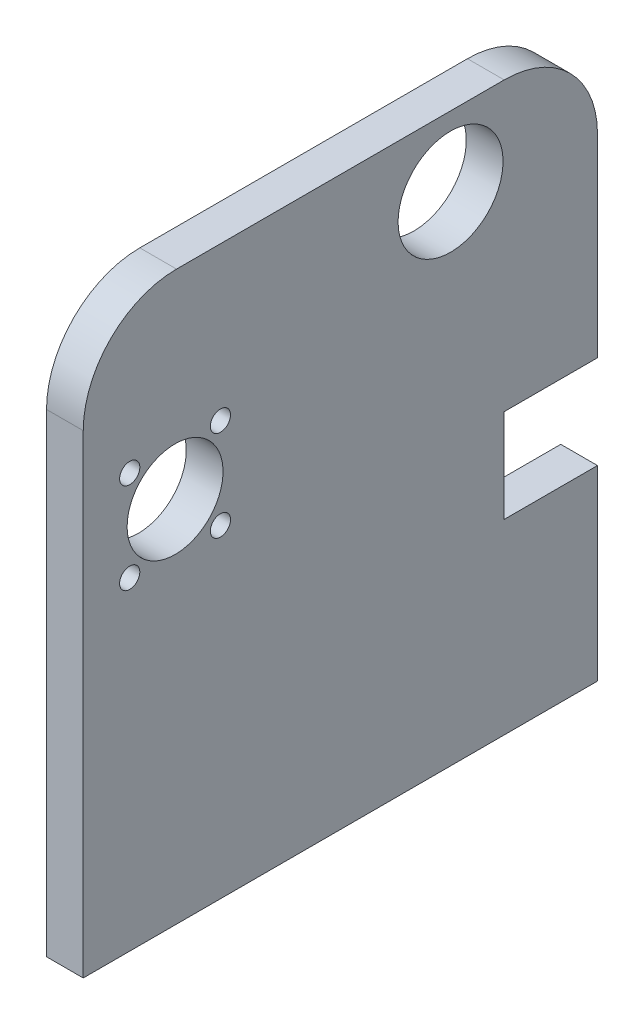
SolidWorks part; units mm, degrees
ref_plane "Front Plane" through (0, 0, 0) normal (0, 0, 1) x (1, 0, 0)
ref_plane "Top Plane" through (0, 0, 0) normal (0, 1, 0) x (1, 0, 0)
ref_plane "Right Plane" through (0, 0, 0) normal (1, 0, 0) x (0, 0, -1)
sketch "Sketch1" plane through (0, 0, 0) normal (0, 1, 0) x (1, 0, 0)
  line L1 (-5, 70) -> (5, 70)
  line L2 (-5, 70) -> (-5, -70)
  line L3 (-5, -70) -> (5, -70)
  line L4 (5, 70) -> (5, -70)
  line L5 (-5, 70) -> (5, -70) construction
  line L6 (-5, -70) -> (5, 70) construction
  point P0 (0, 0)
  dimension "D1" = 140
  dimension "D2" = 10
extrude "Boss-Extrude1" add sketch "Sketch1" along normal mid plane 154.4436
fillet "Fillet1" radius 25.4 2 edges at (0, 77.2218, 70) (0, 77.2218, -70)
sketch "Sketch5" plane through (-5, 0, 0) normal (-1, 0, 0) x (0, 0, 1)
  line L1 (-70, 51.8218) -> (-70, -77.2218) construction
  line L2 (-70, -0.9964) -> (-44.6, -0.9964)
  line L3 (-70, -0.9964) -> (-70, -26.3964)
  line L4 (-70, -26.3964) -> (-44.6, -26.3964)
  line L5 (-70, -77.2218) -> (70, -77.2218) construction
  line L6 (-44.6, -0.9964) -> (-44.6, -26.3964)
  dimension "D3" = 25.4
  dimension "D1" = 50.8254
  dimension "D2" = 25.4
sketch "Sketch3" plane through (-5, 0, 0) normal (-1, 0, 0) x (0, 0, 1)
  line L0 (45, 23.1718) -> (61.409, 39.5809) construction
  line L2 (-70, 51.8218) -> (-70, -77.2218) construction
  line L3 (-45.4613, 23.1718) -> (44.137, 23.1718) construction
  line L6 (45, 46.9613) -> (45, -2.4047) construction
  line L7 (-44.6, 77.2218) -> (44.6, 77.2218) construction
  line L8 (70, 51.8218) -> (70, -77.2218) construction
  circle A0 centre (-30, 58.1718) radius 14.29
  circle A1 centre (32.6521, 35.5197) radius 2.75
  circle A2 centre (57.3479, 35.5197) radius 2.75
  circle A3 centre (32.6521, 10.824) radius 2.75
  circle A4 centre (57.3479, 10.824) radius 2.75
  circle A5 centre (45, 23.1718) radius 13.0556
  circle A6 centre (45, 23.1718) radius 17.4625 construction
  dimension "D1" = 28.58
  dimension "D2" = 19.05
  dimension "D3" = 45
  dimension "D7" = 26.1112
  dimension "D8" = 5.5
  dimension "D10" = 35
  dimension "D11" = 25
  dimension "Bolt circle" = 34.925
  dimension "D9" = 40
extrude "Cut-Extrude2" cut sketch "Sketch3" against normal blind 28.575
extrude "Cut-Extrude4" cut sketch "Sketch5" against normal through all
ref_axis "Axis1" through (5, 58.1718, -30) along (-1, 0, 0)
